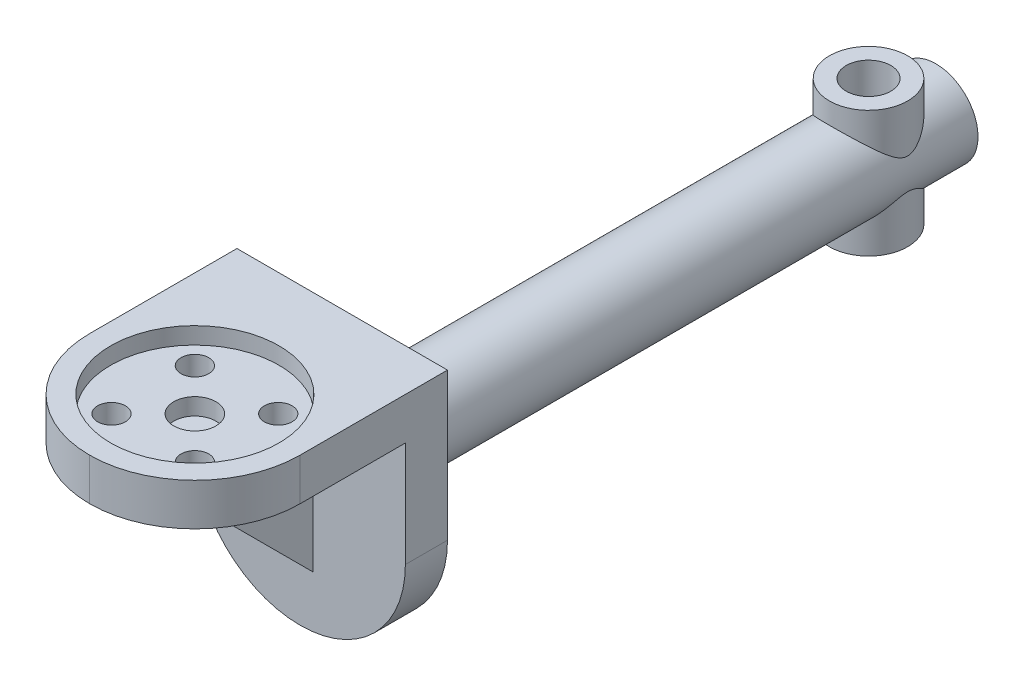
SolidWorks part; units mm, degrees
ref_plane "Front Plane" through (0, 0, 0) normal (1, 0, 0) x (0, 1, 0)
ref_plane "Top Plane" through (0, 0, 0) normal (0, 0, 1) x (0, 1, 0)
ref_plane "Right Plane" through (0, 0, 0) normal (0, 1, 0) x (-1, 0, 0)
sketch "Sketch1" plane through (0, 0, 0) normal (0, 0, 1) x (0, 1, 0)
  circle A0 centre (0, 0) radius 5
  dimension "D1" = 10
extrude "Boss-Extrude1" add sketch "Sketch1" along normal blind 70.5
sketch "Sketch3" plane through (0, 0, 70.5) normal (0, 0, 1) x (1, 0, 0)
  line L5 (-12.5, -15) -> (12.5, -15)
  line L6 (-12.5, -15) -> (-12.5, 15)
  line L7 (-12.5, 15) -> (12.5, 15)
  line L8 (12.5, -15) -> (12.5, 15)
  line L9 (-12.5, -15) -> (12.5, 15) construction
  line L10 (-12.5, 15) -> (12.5, -15) construction
  point P0 (0, 0)
  dimension "D1" = 25
  dimension "D2" = 30
extrude "Boss-Extrude3" add sketch "Sketch3" along normal blind 5
sketch "Sketch4" plane through (0, 0, 75.5) normal (0, 0, 1) x (1, 0, 0)
  line L0 (12.5, -15) -> (12.5, 15) construction
  line L1 (-12.5, 15) -> (12.5, 15)
  line L2 (-12.5, 15) -> (-12.5, 10)
  line L3 (-12.5, 10) -> (12.5, 10)
  line L4 (12.5, 15) -> (12.5, 10)
  dimension "D1" = 5
extrude "Boss-Extrude4" add sketch "Sketch4" along normal blind 25
fillet "Fillet3" radius 12.5 4 edges at (12.5, 12.5, 100.5) (-12.5, 12.5, 100.5) (-12.5, -15, 73) (12.5, -15, 73)
ref_plane "Plane1" through (0, 0, 0) normal (0, 1, 0) x (-1, 0, 0)
sketch "Sketch6" plane through (0, 15, 0) normal (0, 1, 0) x (-1, 0, 0)
  line L0 (-4.9497, 92.9497) -> (4.9497, 83.0503) construction
  line L1 (4.9497, 92.9497) -> (-4.9497, 83.0503) construction
  circle A0 centre (0, 88) radius 10
  circle A1 centre (0, 88) radius 2.5
  circle A2 centre (0, 88) radius 7 construction
  circle A3 centre (-4.9497, 92.9497) radius 1.65
  circle A4 centre (4.9497, 92.9497) radius 1.65
  circle A5 centre (-4.9497, 83.0503) radius 1.65
  circle A6 centre (4.9497, 83.0503) radius 1.65
  dimension "D1" = 20
  dimension "D2" = 5
  dimension "D3" = 14
  dimension "D4" = 3.3
extrude "Cut-Extrude1" cut sketch "Sketch6" against normal up to next contours A3 | A4 | A5 | A6 region at (4.9497, 15, 92.9497) region at (-4.9497, 15, 92.9497) region at (4.9497, 15, 83.0503) region at (-4.9497, 15, 83.0503)
extrude "Cut-Extrude2" cut sketch "Sketch6<3>" against normal blind 2 contours A0 A6 A5 A4 A3 A1 | A4 | A3 | A5 | A6 | A1 region at (9.7172, 15, 88) region at (0, 15, 88) region at (4.9497, 15, 92.9497) region at (-4.9497, 15, 92.9497) region at (4.9497, 15, 83.0503) region at (-4.9497, 15, 83.0503)
sketch "Sketch6<3>" plane through (0, 15, 0) normal (0, 1, 0) x (-1, 0, 0) same geometry as "Sketch6"
extrude "Cut-Extrude3" cut sketch "Sketch6<4>" against normal blind 4 contours A1 region at (0, 15, 88)
sketch "Sketch6<4>" plane through (0, 15, 0) normal (0, 1, 0) x (-1, 0, 0) same geometry as "Sketch6"
fillet "Fillet4" radius 5 1 edges at (5, 0, 70.5)
sketch "Sketch7" plane through (0, 0, 0) normal (0, 1, 0) x (-1, 0, 0)
  circle A0 centre (0, 8) radius 2.65
  circle A2 centre (0, 8) radius 4.65
  dimension "D1" = 5.3
  dimension "D2" = 8
  dimension "D3" = 2
extrude "Cut-Extrude4" cut sketch "Sketch7" against normal up to next and the other way up to next contours A0 region at (0, 0, 8)
extrude "Boss-Extrude6" add sketch "Sketch7<3>" along normal blind 7.5 and the other way blind 7.5
sketch "Sketch7<3>" plane through (0, 0, 0) normal (0, 1, 0) x (-1, 0, 0) same geometry as "Sketch7"
ref_plane "Plane2" through (0, 0, 0) normal (-1, 0, 0) x (0, -1, 0)
sketch "Sketch9" plane through (0, 0, 0) normal (-1, 0, 0) x (0, -1, 0)
  line L0 (-10, 94.25) -> (8.75, 75.5)
  line L1 (-10, 88) -> (-10, 100.5) construction
  line L2 (15, 75.5) -> (2.5, 75.5) construction
  line L3 (8.75, 75.5) -> (-10, 75.5)
  line L4 (-10, 75.5) -> (-10, 94.25)
extrude "Boss-Extrude7" add sketch "Sketch9" along normal blind 1.5 and the other way blind 1.5
